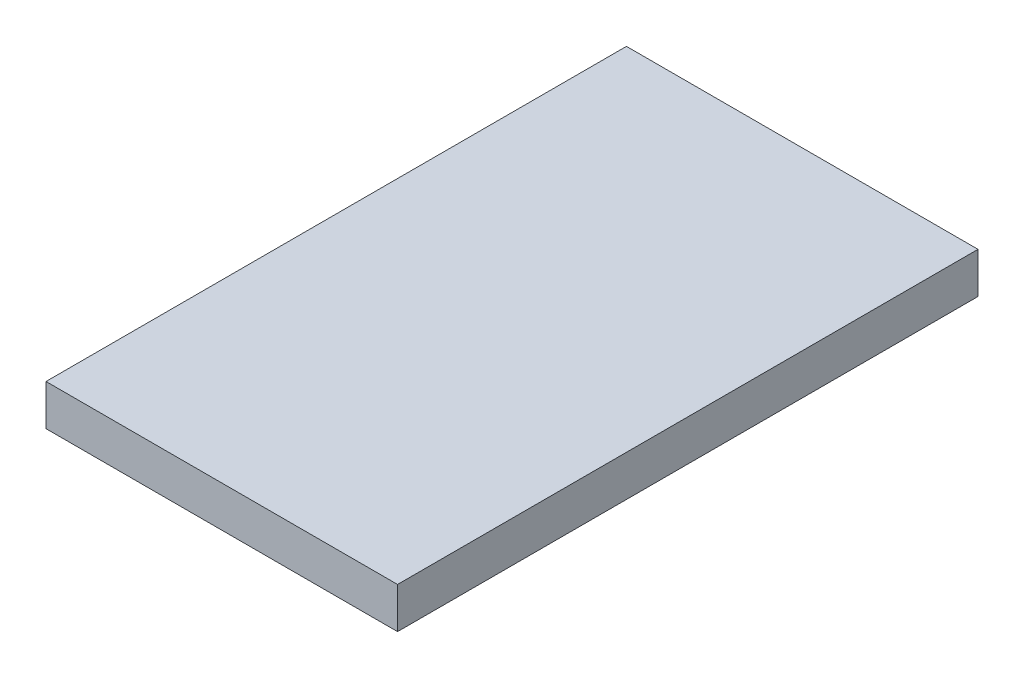
SolidWorks part; units mm, degrees
ref_plane "Front Plane" through (0, 0, 0) normal (0, 0, 1) x (1, 0, 0)
ref_plane "Top Plane" through (0, 0, 0) normal (0, 1, 0) x (1, 0, 0)
ref_plane "Right Plane" through (0, 0, 0) normal (1, 0, 0) x (0, 0, -1)
sketch "Sketch1" plane through (0, 0, 0) normal (0, 1, 0) x (1, 0, 0)
  line L1 (0, 0) -> (-54.61, 0)
  line L2 (0, 0) -> (0, 90.17)
  line L3 (0, 90.17) -> (-54.61, 90.17)
  line L4 (-54.61, 0) -> (-54.61, 90.17)
  dimension "D1" = 90.17
  dimension "D2" = 54.61
extrude "Boss-Extrude1" add sketch "Sketch1" along normal blind 6.35
ref_plane "KORAL!!!" through (-27.305, 0, 0) normal (1, 0, 0) x (0, 0, -1)
sketch "Sketch3" plane through (0, 0, 0) normal (0, 0, 1) x (1, 0, 0)
  line L6 (-54.61, 6.35) -> (0, 6.35)
  line L7 (-54.61, 6.35) -> (-54.61, 0)
  line L8 (-54.61, 0) -> (0, 0)
  line L9 (0, 6.35) -> (0, 0)
  dimension "D1" = 54.61
extrude "Boss-Extrude2" add sketch "Sketch3" against normal up to surface (90.17 mm away) up to face at (-27.305, 3.175, -90.17)
